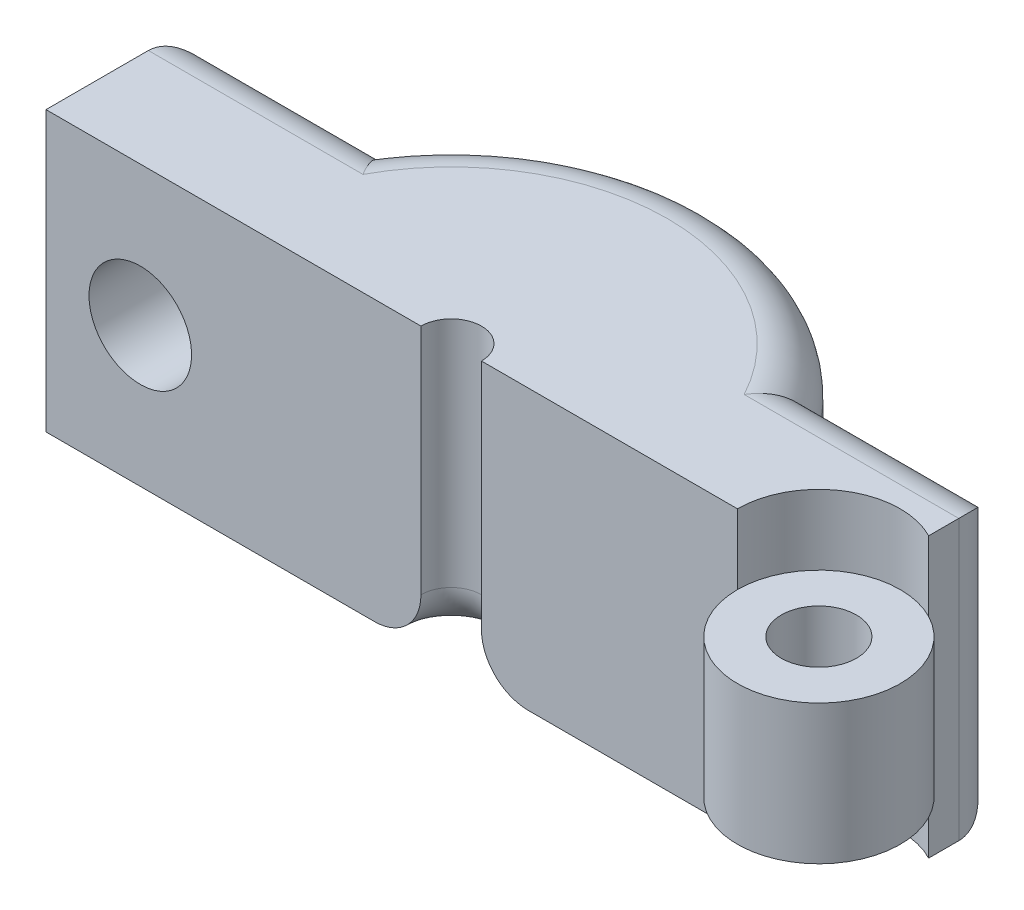
SolidWorks part; units mm, degrees
ref_plane "Front Plane" through (0, 0, 0) normal (0, 0, 1) x (1, 0, 0)
ref_plane "Top Plane" through (0, 0, 0) normal (0, 1, 0) x (1, 0, 0)
ref_plane "Right Plane" through (0, 0, 0) normal (1, 0, 0) x (0, 0, -1)
sketch "Sketch1" plane through (0, 0, 0) normal (0, 1, 0) x (1, 0, 0)
  line L0 (-22.12, 0) -> (-1.651, 0)
  line L2 (0, 0) -> (0, 14.351) construction
  line L3 (-11.8274, 8.128) -> (-22.12, 8.128)
  line L6 (-22.12, 8.128) -> (-22.12, 0)
  line L7 (15.625, 0) -> (1.651, 0)
  line L8 (11.8274, 8.128) -> (22.12, 8.128)
  line L9 (22.12, 8.128) -> (22.12, 3.944)
  line L10 (20.07, 0) -> (22.12, 0) construction
  arc A0 (1.651, 0) -> (-1.651, 0) centre (0, 0) ccw
  arc A1 (11.8274, 8.128) -> (-11.8274, 8.128) centre (0, 0) ccw
  arc A3 (15.625, 0) -> (22.12, 3.944) centre (20.07, 0) ccw
  circle A4 centre (20.07, 0) radius 2.05
  dimension "D1" = 3.302
  dimension "D2" = 12.7
  dimension "D5" = 4.445
  dimension "4.1mm" = 4.1
  dimension "D3" = 20.07
  dimension "D4" = 8.128
extrude "Boss-Extrude1" add sketch "Sketch1" along normal blind 15.24
ref_plane "Plane1" through (0, 7.62, 0) normal (0, 1, 0) x (1, 0, 0)
sketch "Sketch2" plane through (0, 7.62, 0) normal (0, 1, 0) x (1, 0, 0)
  circle A0 centre (20.07, 0) radius 4.445
  arc A1 (15.625, 0) -> (22.12, 3.944) centre (20.07, 0) ccw construction
extrude "Cut-Extrude1" cut sketch "Sketch2" against normal mid plane 8.001
sketch "Sketch3" plane through (0, 0, -8.128) normal (0, 0, -1) x (-1, 0, 0)
  line L0 (11.8274, 7.62) -> (22.12, 7.62) construction
  line L1 (11.8274, 15.24) -> (11.8274, 0) construction
  line L2 (22.12, 15.24) -> (22.12, 0) construction
  circle A0 centre (16.9737, 7.62) radius 2.8
  dimension "D1" = 5.6
extrude "Cut-Extrude2" cut sketch "Sketch3" against normal up to surface (8.128 mm away) up to face at (-11.8855, 7.62, 0)
fillet "Fillet1" radius 2.54 8 edges at (0, 0, -14.351) (16.9737, 0, -8.128) (-16.9737, 0, -8.128) (-16.9737, 15.24, -8.128) (16.9737, 15.24, -8.128) (0, 15.24, -14.351) (-22.12, 7.62, -8.128) (22.12, 7.62, -8.128)
fillet "Fillet2" radius 2.54 1 edges at (0, 0, -1.651)
sketch "Sketch4" plane through (0, 7.62, 0) normal (0, 1, 0) x (1, 0, 0)
  circle A0 centre (20.07, 0) radius 4.445
  circle A1 centre (20.07, 0) radius 2.05 construction
  circle A2 centre (20.07, 0) radius 2.05
extrude "Boss-Extrude2" add sketch "Sketch4" along normal blind 3.8 and the other way blind 3.8
sketch "Sketch5" plane through (0, 3.6195, 0) normal (0, 1, 0) x (1, 0, 0)
  arc A2 (22.12, 3.944) -> (15.625, 0) centre (20.07, 0) ccw
  arc A3 (15.625, 0) -> (22.12, 3.944) centre (20.07, 0) ccw
  arc A4 (22.12, 3.944) -> (15.625, 0) centre (20.07, 0) ccw
  arc A5 (15.625, 0) -> (22.12, 3.944) centre (20.07, 0) ccw
  dimension "D1" = 0
extrude "Cut-Extrude3" cut sketch "Sketch5" against normal through all
sketch "Sketch6" plane through (0, 11.6205, 0) normal (0, -1, 0) x (1, 0, 0)
  arc A2 (15.625, 0) -> (22.12, -3.944) centre (20.07, 0) ccw
  arc A3 (22.12, -3.944) -> (15.625, 0) centre (20.07, 0) ccw
  arc A4 (15.625, 0) -> (22.12, -3.944) centre (20.07, 0) ccw
  arc A5 (22.12, -3.944) -> (15.625, 0) centre (20.07, 0) ccw
  dimension "D1" = 0
extrude "Cut-Extrude4" cut sketch "Sketch6" against normal through all
